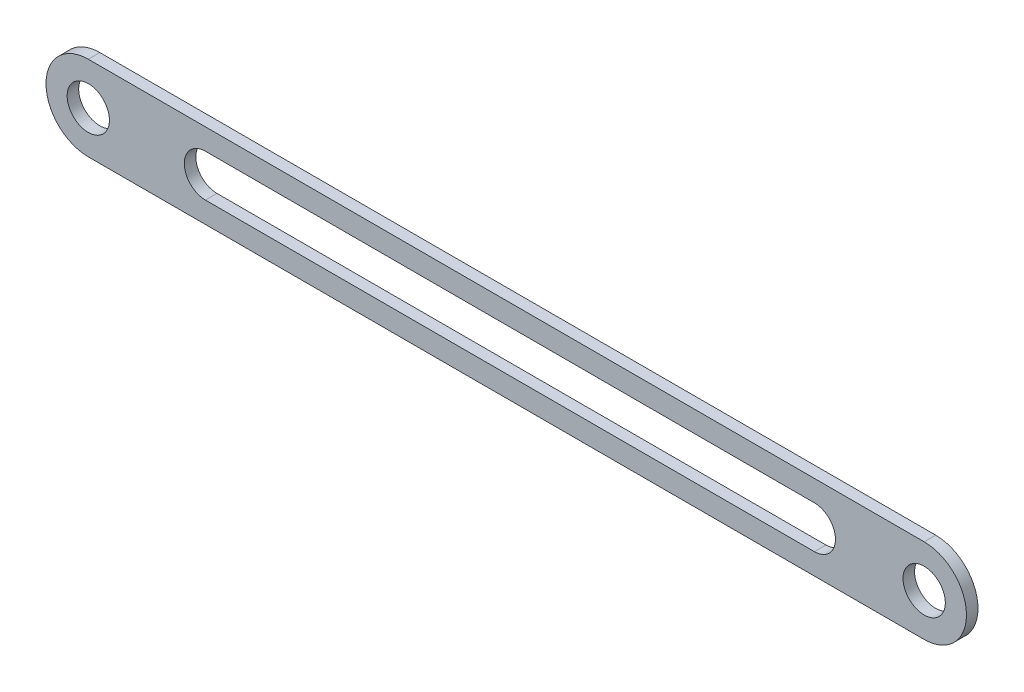
SolidWorks part; units mm, degrees
material "Cast Alloy Steel"
ref_plane "Front Plane" through (0, 0, 0) normal (0, 0, 1) x (1, 0, 0)
ref_plane "Top Plane" through (0, 0, 0) normal (0, 1, 0) x (1, 0, 0)
ref_plane "Right Plane" through (0, 0, 0) normal (1, 0, 0) x (0, 0, -1)
sketch "Sketch1" plane through (0, 0, 0) normal (0, 0, 1) x (1, 0, 0)
  line L0 (-108.725, 0) -> (108.725, 0) construction
  line L1 (-108.725, 11) -> (108.725, 11)
  line L2 (-108.725, -11) -> (108.725, -11)
  line L3 (0, 31.5598) -> (0, -22.2851) construction
  line L4 (-78.255, 0) -> (80.145, 0) construction
  line L5 (-78.255, 5.5) -> (80.145, 5.5)
  line L6 (-78.255, -5.5) -> (80.145, -5.5)
  arc A0 (-108.725, 11) -> (-108.725, -11) centre (-108.725, 0) ccw
  arc A1 (108.725, -11) -> (108.725, 11) centre (108.725, 0) ccw
  circle A2 centre (-108.725, 0) radius 5.5
  circle A3 centre (108.725, 0) radius 5.5
  arc A4 (-78.255, 5.5) -> (-78.255, -5.5) centre (-78.255, 0) ccw
  arc A5 (80.145, -5.5) -> (80.145, 5.5) centre (80.145, 0) ccw
  point P3 (0, 0)
  point P16 (0.945, 0)
  point P21 (-83.755, 0)
  point P22 (85.645, 0)
  dimension "D1" = 11
  dimension "D2" = 11
  dimension "D3" = 217.45
  dimension "D5" = 192.48
  dimension "D4" = 11
  dimension "D6" = 23.08
extrude "Boss-Extrude1" add sketch "Sketch1" along normal blind 3
